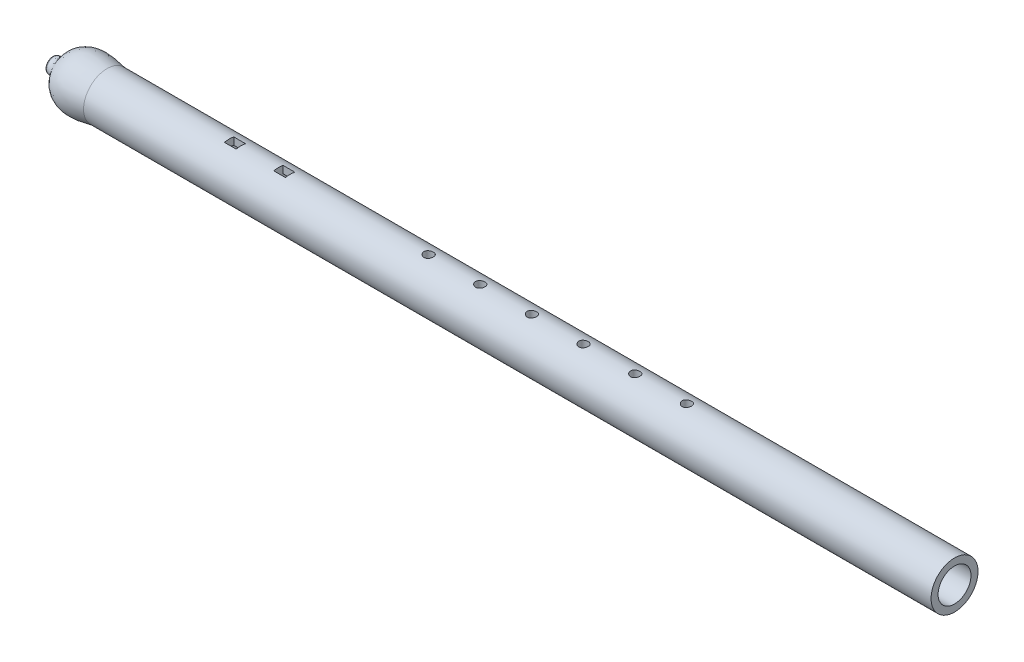
SolidWorks part; units mm, degrees
ref_plane "Front Plane" through (0, 0, 0) normal (0, 0, 1) x (1, 0, 0)
ref_plane "Top Plane" through (0, 0, 0) normal (0, 1, 0) x (1, 0, 0)
ref_plane "Right Plane" through (0, 0, 0) normal (1, 0, 0) x (0, 0, -1)
sketch "Sketch1" plane through (0, 0, 0) normal (1, 0, 0) x (0, 0, -1)
  line L1 (-19.05, 19.05) -> (19.05, 19.05)
  line L2 (-19.05, 19.05) -> (-19.05, -19.05)
  line L3 (-19.05, -19.05) -> (19.05, -19.05)
  line L4 (19.05, 19.05) -> (19.05, -19.05)
  line L5 (-19.05, 19.05) -> (19.05, -19.05) construction
  line L6 (-19.05, -19.05) -> (19.05, 19.05) construction
  point P0 (0, 0)
  dimension "D1" = 38.1
  dimension "D2" = 38.1
extrude "Boss-Extrude1" add sketch "Sketch1" along normal mid plane 609.6
sketch "Sketch2" plane through (0, 0, 0) normal (0, 1, 0) x (1, 0, 0)
  line L0 (-304.8, 0) -> (304.8, 0) construction
  line L1 (-304.8, 19.05) -> (-304.8, -19.05) construction
  line L2 (304.8, 19.05) -> (304.8, -19.05) construction
  line L3 (304.8, 0) -> (-152.4, 0)
  line L4 (-152.4, -11.1125) -> (304.8, -11.1125)
  line L5 (304.8, -11.1125) -> (304.8, 0)
  line L6 (-177.8, 0) -> (-279.4, 0)
  line L7 (-268.2875, -11.1125) -> (-177.8, -11.1125)
  line L8 (-177.8, 0) -> (-177.8, -11.1125)
  line L10 (-152.4, -11.1125) -> (-152.4, 0)
  arc A1 (-279.4, 0) -> (-268.2875, -11.1125) centre (-268.2875, 0) ccw
  dimension "D1" = 11.1125
  dimension "D2" = 457.2
  dimension "D3" = 101.6
  dimension "D4" = 25.4
  dimension "D5" = 25.4
revolve "Cut-Revolve1" cut sketch "Sketch2" angle 360 about L0
sketch "Sketch4" plane through (-304.8, 0, 0) normal (-1, 0, 0) x (0, 0, 1)
  circle A0 centre (0, 0) radius 4.7625
  dimension "D1" = 9.525
extrude "Cut-Extrude1" cut sketch "Sketch4" against normal blind 50.8
sketch "Sketch3" plane through (0, 0, 0) normal (0, 0, 1) x (1, 0, 0)
  line L0 (-304.8, 0) -> (304.8, 0) construction
  line L1 (-304.8, -19.05) -> (-304.8, 19.05) construction
  line L2 (304.8, -11.1125) -> (304.8, 11.1125) construction
  line L3 (304.8, 19.05) -> (304.8, 15.875)
  line L4 (304.8, -19.05) -> (304.8, 19.05) construction
  line L5 (304.8, 15.875) -> (-268.2875, 15.875)
  line L6 (-268.2875, 15.875) -> (-300.0526, 23.3466) construction
  line L7 (-300.0526, 23.3466) -> (-295.1779, 6.1989) construction
  line L8 (-295.1779, 6.1989) -> (-299.7052, 5.3196) construction
  line L9 (-299.7052, 5.3196) -> (-304.8, 5.08) construction
  line L10 (-304.8, 5.08) -> (-304.8, 19.05)
  line L11 (-304.8, 19.05) -> (-304.8, 56.3779)
  line L12 (-304.8, 56.3779) -> (304.8, 56.3779)
  line L13 (304.8, 56.3779) -> (304.8, 19.05)
  line L14 (-268.2875, 11.1125) -> (-268.2875, 15.875) construction
  line L15 (-37.722, 56.3779) -> (-37.722, 15.875)
  spline S0 degree 4 poles (-268.2875, 15.875) (-300.0526, 23.3466) (-295.1779, 6.1989) (-299.7052, 5.3196) (-304.8, 5.08) knots 0 0 0 0 0 1 1 1 1 1
  dimension "D1" = 15.875
  dimension "D2" = 5.08
revolve "Cut-Revolve2" cut sketch "Sketch3" angle 360 about L0 region at (133.539, 36.1265, 0) region at (-172.0564, 35.9725, 0)
fillet "Fillet1" radius 1.27 1 edges at (-304.8, -5.08, 0)
sketch "Sketch5" plane through (0, 0, 0) normal (0, 1, 0) x (1, 0, 0)
  line L0 (304.8, 0) -> (123.825, 0) construction
  line L1 (304.8, -15.875) -> (304.8, 15.875) construction
  line L2 (123.825, 0) -> (88.9, 0) construction
  line L3 (88.9, 0) -> (53.975, 0) construction
  line L4 (53.975, 0) -> (19.05, 0) construction
  line L5 (19.05, 0) -> (-15.875, 0) construction
  line L6 (-15.875, 0) -> (-50.8, 0) construction
  line L7 (-50.8, 0) -> (-304.8, 0) construction
  line L8 (-304.8, 3.8943) -> (-304.8, -3.8943) construction
  line L9 (-152.4, -11.1125) -> (-152.4, 11.1125) construction
  circle A0 centre (-50.8, 0) radius 3.175
  circle A1 centre (-15.875, 0) radius 3.175
  circle A2 centre (19.05, 0) radius 3.175
  circle A3 centre (53.975, 0) radius 3.175
  circle A4 centre (88.9, 0) radius 3.175
  circle A5 centre (123.825, 0) radius 3.175
  dimension "D1" = 6.35
  dimension "D2" = 34.925
  dimension "D3" = 101.6
extrude "Cut-Extrude2" cut sketch "Sketch5" along normal through all
ref_plane "Plane1" through (0, 15.875, 0) normal (0, 1, 0) x (1, 0, 0)
sketch "Sketch6" plane through (0, 15.875, 0) normal (0, 1, 0) x (1, 0, 0)
  line L0 (-177.8, 11.1125) -> (-177.8, -11.1125) construction
  line L1 (-185.7375, -3.175) -> (-177.8, -3.175)
  line L2 (-185.7375, -3.175) -> (-185.7375, 3.175)
  line L3 (-185.7375, 3.175) -> (-177.8, 3.175)
  line L4 (-177.8, -3.175) -> (-177.8, 3.175)
  line L5 (-185.7375, -3.175) -> (-177.8, 3.175) construction
  line L6 (-185.7375, 3.175) -> (-177.8, -3.175) construction
  line L7 (0, 0) -> (-181.7688, 0) construction
  line L8 (-152.4, -11.1125) -> (-152.4, 11.1125) construction
  line L9 (-144.4625, 3.175) -> (-152.4, 3.175)
  line L10 (-144.4625, 3.175) -> (-144.4625, -3.175)
  line L11 (-144.4625, -3.175) -> (-152.4, -3.175)
  line L12 (-152.4, 3.175) -> (-152.4, -3.175)
  line L13 (-144.4625, 3.175) -> (-152.4, -3.175) construction
  line L14 (-144.4625, -3.175) -> (-152.4, 3.175) construction
  point P0 (-181.7688, 0)
  point P10 (-148.4312, 0)
  dimension "D1" = 7.9375
  dimension "D2" = 6.35
extrude "Cut-Extrude3" cut sketch "Sketch6" against normal blind 6.35
chamfer "Chamfer1" distance 3.81 angle 45 1 edges at (-144.4625, 11.1125, 0)
fillet "Fillet2" radius 19.05 rebuild error yes
